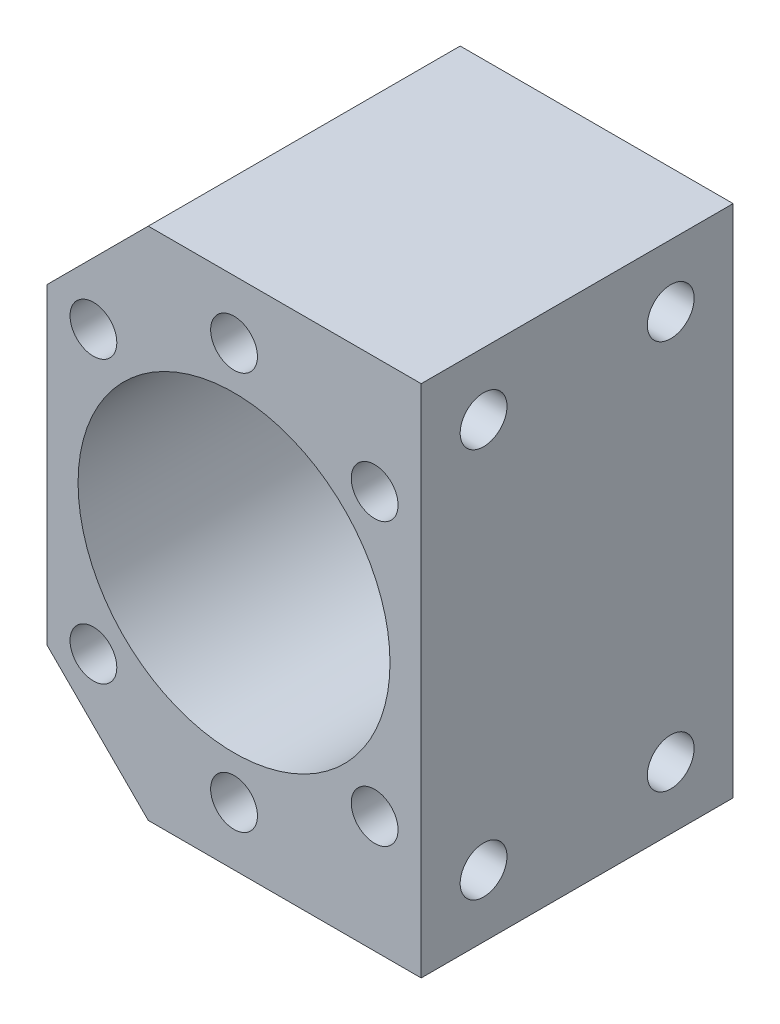
SolidWorks part; units mm, degrees
ref_plane "Front Plane" through (0, 0, 0) normal (0, 0, 1) x (1, 0, 0)
ref_plane "Top Plane" through (0, 0, 0) normal (0, 1, 0) x (1, 0, 0)
ref_plane "Right Plane" through (0, 0, 0) normal (1, 0, 0) x (0, 0, -1)
sketch "Sketch1" plane through (0, 0, 0) normal (0, 0, 1) x (1, 0, 0)
  line L0 (-24, -20) -> (-11, -33)
  line L1 (-11, -33) -> (24, -33)
  line L2 (-24, -20) -> (-24, 20)
  line L3 (-11, 33) -> (24, 33)
  line L4 (24, -33) -> (24, 33)
  line L5 (-24, 20) -> (-24, 33) construction
  line L6 (-24, 33) -> (-11, 33) construction
  line L12 (-24, -20) -> (-11, -33) construction
  line L13 (-35.8332, 0) -> (27.1872, 0) construction
  line L14 (-24, 20) -> (-11, 33)
  circle A0 centre (0, 0) radius 20
  point P0 (0, 0)
  point P16 (-20.9054, -23.0946)
  point P28 (0, 0)
  dimension "D" = 40
  dimension "B" = 66
  dimension "H" = 48
  dimension "h1" = 24
  dimension "E" = 13
extrude "Boss-Extrude2" add sketch "Sketch1" along normal blind 40 contours L2 L14 L3 L4 L1 L0 | A0
sketch "Sketch8" plane through (0, 0, 40) normal (0, 0, 1) x (1, 0, 0)
  line L0 (-18.0312, -18.0312) -> (18.0312, 18.0312) construction
  line L1 (-18.0312, 18.0312) -> (18.0312, -18.0312) construction
  line L2 (0, 25.5) -> (0, -25.5) construction
  circle A1 centre (0, 25.5) radius 3
  circle A2 centre (18.0312, 18.0312) radius 3
  circle A4 centre (18.0312, -18.0312) radius 3
  circle A5 centre (0, -25.5) radius 3
  circle A6 centre (-18.0312, -18.0312) radius 3
  circle A8 centre (-18.0312, 18.0312) radius 3
  circle A9 centre (25.5, 0) radius 3 [skipped]
  circle A10 centre (-25.5, 0) radius 3 [skipped]
  point P22 (0, 0)
  dimension "D1" = 8
  dimension "Y" = 6
  dimension "W" = 51
extrude "Cut-Extrude1" cut sketch "Sketch8" against normal blind 16
sketch "Sketch9" plane through (24, 0, 0) normal (1, 0, 0) x (0, 0, -1)
  line L1 (0, 0) -> (-40, 0) construction
  line L2 (-40, -33) -> (-40, 33) construction
  line L10 (-32, 25) -> (-32, -25) construction
  line L11 (-8, 25) -> (-8, -25) construction
  line L12 (11.1909, 25) -> (-32, 25) construction
  line L13 (0, 0) -> (11.1909, 0) construction
  line L14 (11.1909, -25) -> (11.1909, 25) construction
  line L15 (11.1909, -25) -> (-32, -25) construction
  circle A1 centre (-32, 25) radius 3
  circle A2 centre (-8, 25) radius 3
  circle A3 centre (-8, -25) radius 3
  circle A4 centre (-32, -25) radius 3
  point P4 (-20, 0)
  point P8 (11.1909, 0)
  dimension "X" = 6
  dimension "C2" = 24
  dimension "C1" = 8
  dimension "P" = 50
extrude "Cut-Extrude2" cut sketch "Sketch9" against normal blind 16
chamfer "Chamfer1" [suppressed] distance 0.5 angle 45
